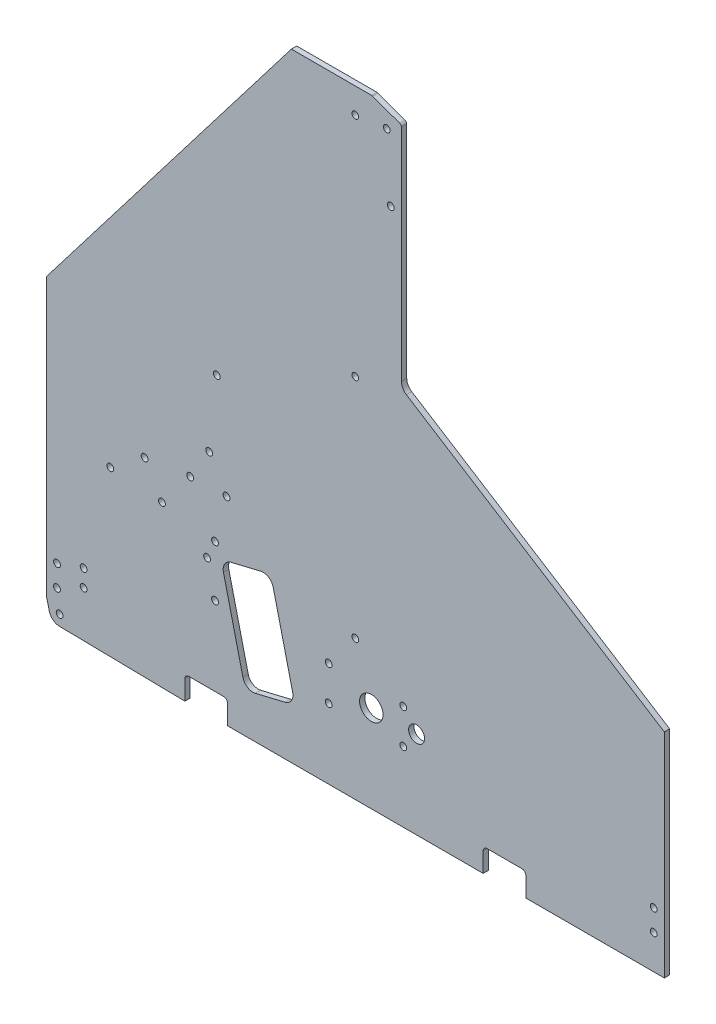
SolidWorks part; units mm, degrees
ref_plane "Front Plane" through (0, 0, 0) normal (0, 0, 1) x (1, 0, 0)
ref_plane "Top Plane" through (0, 0, 0) normal (0, 1, 0) x (1, 0, 0)
ref_plane "Right Plane" through (0, 0, 0) normal (1, 0, 0) x (0, 0, -1)
sketch "Sketch1" plane through (0, 0, 0) normal (0, 0, 1) x (1, 0, 0)
  line L0 (82.55, -20.32) -> (82.55, -6.35)
  line L2 (0, 0) -> (0, 157.48)
  line L4 (368.3, -20.32) -> (368.3, 106.68)
  line L5 (82.55, -6.35) -> (107.95, -6.35)
  line L6 (107.95, -6.35) -> (107.95, -20.32)
  line L7 (107.95, -20.32) -> (260.35, -20.32)
  line L8 (260.35, -20.32) -> (260.35, -6.35)
  line L9 (260.35, -6.35) -> (285.75, -6.35)
  line L10 (285.75, -6.35) -> (285.75, -20.32)
  line L11 (285.75, -20.32) -> (368.3, -20.32)
  line L12 (361.95, 12.7) -> (368.3, 12.7) construction
  line L13 (0, 0) -> (6.35, 0) construction
  line L14 (0.1896, -7.8901) -> (1.7771, -14.2401)
  line L15 (7.8295, -19.0491) -> (82.55, -20.32)
  line L16 (0, 0) -> (0, -6.35)
  line L17 (85.725, 97.155) -> (82.9754, 95.5675) construction
  line L18 (97.0634, 115.6163) -> (58.5686, 93.3913) construction
  line L19 (97.0634, 115.6163) -> (107.3822, 97.7437) construction
  line L20 (58.5686, 93.3913) -> (68.8873, 75.5187) construction
  line L21 (107.3822, 97.7437) -> (68.8873, 75.5187) construction
  line L22 (97.0634, 115.6163) -> (68.8873, 75.5187) construction
  line L23 (58.5686, 93.3913) -> (107.3822, 97.7437) construction
  line L24 (7.9375, -12.7) -> (95.7973, 60.4105) construction
  line L25 (184.15, 62.98) -> (184.15, 197.98) construction
  line L26 (184.15, 197.98) -> (184.15, 332.98) construction
  line L27 (355.6, 335.28) -> (330.2, 335.28) construction
  line L28 (330.2, 335.28) -> (330.2, 220.98) construction
  line L29 (330.2, 220.98) -> (355.6, 220.98) construction
  line L30 (355.6, 220.98) -> (355.6, 335.28) construction
  line L31 (184.15, 347.98) -> (184.15, 269.4703) construction
  line L32 (12.7, 335.28) -> (38.1, 335.28) construction
  line L33 (38.1, 335.28) -> (38.1, 220.98) construction
  line L34 (12.7, 220.98) -> (12.7, 335.28) construction
  line L35 (38.1, 220.98) -> (12.7, 220.98) construction
  line L36 (194.15, 347.98) -> (211.6138, 341.63)
  line L37 (184.15, 347.98) -> (146.05, 347.98)
  line L38 (184.15, 347.98) -> (194.15, 347.98)
  line L39 (348.5362, 347.98) -> (413.4623, 347.98)
  line L40 (348.5362, 347.98) -> (211.6138, 347.98) construction
  line L42 (146.05, 347.98) -> (0, 157.48)
  line L44 (211.6138, 341.63) -> (211.6138, 205.74)
  line L45 (211.6138, 205.74) -> (368.3, 106.68)
  line L46 (194.15, 347.98) -> (-141.0713, 347.98) construction
  circle A0 centre (6.35, 0) radius 2.032
  circle A1 centre (6.35, 12.7) radius 2.032
  circle A2 centre (361.95, 0) radius 2.032
  circle A3 centre (361.95, 12.7) radius 2.032
  arc A5 (1.7771, -14.2401) -> (7.8295, -19.0491) centre (7.9375, -12.7) ccw
  circle A6 centre (7.9375, -12.7) radius 2.032
  arc A7 (0, -6.35) -> (0.1896, -7.8901) centre (6.35, -6.35) ccw
  circle A8 centre (38.1, 78.105) radius 2.032
  circle A9 centre (85.725, 97.155) radius 2.032
  circle A10 centre (58.5686, 93.3913) radius 2.032
  circle A11 centre (68.8873, 75.5187) radius 2.032
  circle A12 centre (107.3822, 97.7437) radius 2.032
  circle A13 centre (97.0634, 115.6163) radius 2.032
  circle A14 centre (95.7973, 60.4105) radius 2.032
  circle A15 centre (184.15, 62.98) radius 2
  circle A16 centre (184.15, 197.98) radius 2
  circle A17 centre (184.15, 332.98) radius 2
  circle A18 centre (63.5, 316.23) radius 2.032
  circle A19 centre (101.6, 157.48) radius 2.032
  circle A20 centre (355.6, 335.28) radius 2.032
  circle A21 centre (330.2, 335.28) radius 2.032
  circle A22 centre (355.6, 220.98) radius 2.032
  circle A23 centre (330.2, 220.98) radius 2.032
  circle A24 centre (12.7, 335.28) radius 2.032
  circle A25 centre (38.1, 335.28) radius 2.032
  circle A26 centre (12.7, 220.98) radius 2.032
  circle A27 centre (38.1, 220.98) radius 2.032
  circle A28 centre (202.8819, 335.28) radius 2
  circle A29 centre (205.2638, 296.418) radius 2.032
  point P82 (184.15, 347.98)
  point P83 (202.8819, 344.805)
  dimension "D6" = 4.064
  dimension "D10" = 6.35
  dimension "D11" = 4.064
  dimension "D17" = 38.1
  dimension "D27" = 4
  dimension "D31" = 4.064
  dimension "D32" = 38.1
  dimension "D36" = 4.064
  dimension "D47" = 45.212
  dimension "D48" = 4.064
  dimension "D2" = 127
  dimension "D3" = 13.97
  dimension "D4" = 25.4
  dimension "D5" = 152.4
  dimension "D7" = 12.7
  dimension "D8" = 6.35
  dimension "D9" = 20.32
  dimension "D12" = 12.7
  dimension "D13" = 1.5875
  dimension "D14" = 82.55
  dimension "D15" = 368.3
  dimension "D16" = 6.35
  dimension "D18" = 98.425
  dimension "D19" = 47.625
  dimension "D20" = 19.05
  dimension "D21" = 3.175
  dimension "D22" = 60
  dimension "D23" = 20.6375
  dimension "D24" = 44.45
  dimension "D25" = 38.1
  dimension "D26" = 114.3
  dimension "D28" = 135
  dimension "D29" = 12.7
  dimension "D30" = 15
  dimension "D33" = 63.5
  dimension "D34" = 27.4638
  dimension "D35" = 101.6
  dimension "D37" = 114.3
  dimension "D38" = 25.4
  dimension "D39" = 12.7
  dimension "D40" = 157.48
  dimension "D41" = 142.24
  dimension "D42" = 368.3
  dimension "D43" = 10
  dimension "D44" = 6.35
  dimension "D45" = 31.75
  dimension "D46" = 6.35
  dimension "D49" = 6.35
extrude "Boss-Extrude1" add sketch "Sketch1" along normal blind 3.175 contours L16 A7 L14 A5 L15 L2 A0 A1 A6 region at (167.8922, 118.3155, 0)
fillet "Fillet1" radius 2.286 4 edges at (285.75, -6.35, 1.5875) (107.95, -6.35, 1.5875) (260.35, -6.35, 1.5875) (82.55, -6.35, 1.5875)
fillet "Fillet2" radius 6.35 1 edges at (211.6138, 205.74, 1.5875)
sketch "Sketch2" plane through (0, 0, 0) normal (0, 0, -1) x (-1, 0, 0)
  circle A0 centre (-100.5528, 71.086) radius 2.032 construction
  circle A1 centre (-100.5528, 40.606) radius 2.032 construction
  circle A2 centre (-22.225, 18.2025) radius 2.032 construction
  circle A3 centre (-22.225, 8.0425) radius 2.032 construction
  circle A4 centre (-100.5528, 71.086) radius 2.032
  circle A5 centre (-100.5528, 40.606) radius 2.032
  circle A6 centre (-22.225, 18.2025) radius 2.032
  circle A7 centre (-22.225, 8.0425) radius 2.032
extrude "Cut-Extrude1" cut sketch "Sketch2" against normal through all
fillet "Fillet3" radius 1.5875 2 edges at (211.6138, 341.63, 1.5875) (194.15, 347.98, 1.5875)
sketch "Sketch3" plane through (0, 0, 3.175) normal (0, 0, 1) x (1, 0, 0)
  line L0 (132.9524, 63.2646) -> (132.7215, 64.2281) construction
  line L1 (128.3814, 66.8897) -> (110.6828, 62.6472) construction
  line L2 (114.5132, 58.4237) -> (126.8822, 61.3887) construction
  line L3 (108.0212, 58.3071) -> (108.2522, 57.3436) construction
  line L4 (131.2006, 57.703) -> (140.0164, 20.9265) construction
  line L5 (144.0993, 16.7636) -> (132.9524, 63.2646) construction
  line L6 (108.2522, 57.3436) -> (119.3991, 10.8426) construction
  line L7 (121.1509, 16.4042) -> (112.3351, 53.1807) construction
  line L8 (119.3991, 10.8426) -> (119.6301, 9.8791) construction
  line L9 (144.3303, 15.8001) -> (144.0993, 16.7636) construction
  line L10 (137.8383, 15.6835) -> (125.4694, 12.7185) construction
  line L11 (123.9701, 7.2175) -> (141.6687, 11.4601) construction
  line L12 (132.9524, 63.2646) -> (132.7215, 64.2281)
  line L13 (128.3814, 66.8897) -> (110.6828, 62.6472)
  line L14 (114.5132, 58.4237) -> (126.8822, 61.3887)
  line L15 (108.0212, 58.3071) -> (108.2522, 57.3436)
  line L16 (131.2006, 57.703) -> (140.0164, 20.9265)
  line L17 (144.0993, 16.7636) -> (132.9524, 63.2646)
  line L18 (108.2522, 57.3436) -> (119.3991, 10.8426)
  line L19 (121.1509, 16.4042) -> (112.3351, 53.1807)
  line L20 (119.3991, 10.8426) -> (119.6301, 9.8791)
  line L21 (144.3303, 15.8001) -> (144.0993, 16.7636)
  line L22 (137.8383, 15.6835) -> (125.4694, 12.7185)
  line L23 (123.9701, 7.2175) -> (141.6687, 11.4601)
  line L24 (127.7894, 69.3598) -> (110.0908, 65.1172)
  line L25 (105.5512, 57.715) -> (105.7822, 56.7515)
  line L26 (105.7822, 56.7515) -> (116.9291, 10.2505)
  line L27 (116.9291, 10.2505) -> (117.16, 9.287)
  line L28 (124.5622, 4.7475) -> (142.2608, 8.99)
  line L29 (146.8003, 16.3922) -> (146.5694, 17.3557)
  line L30 (146.5694, 17.3557) -> (135.4225, 63.8567)
  line L31 (135.4225, 63.8567) -> (135.1915, 64.8202)
  arc A0 (132.7215, 64.2281) -> (128.6308, 66.9403) centre (129.2206, 63.3889) ccw construction
  arc A1 (110.6828, 62.6472) -> (110.4377, 62.5791) centre (111.522, 59.1463) ccw construction
  arc A2 (128.6308, 66.9403) -> (128.3814, 66.8897) centre (129.2206, 63.3889) ccw construction
  arc A3 (110.4377, 62.5791) -> (108.0212, 58.3071) centre (111.522, 59.1463) ccw construction
  arc A4 (119.6301, 9.8791) -> (123.7207, 7.1669) centre (123.1309, 10.7183) ccw construction
  arc A5 (141.9139, 11.5281) -> (144.3303, 15.8001) centre (140.8295, 14.9609) ccw construction
  arc A6 (141.6687, 11.4601) -> (141.9139, 11.5281) centre (140.8295, 14.9609) ccw construction
  arc A7 (123.7207, 7.1669) -> (123.9701, 7.2175) centre (123.1309, 10.7183) ccw construction
  arc A8 (132.7215, 64.2281) -> (128.6308, 66.9403) centre (129.2206, 63.3889) ccw
  arc A9 (110.6828, 62.6472) -> (110.4377, 62.5791) centre (111.522, 59.1463) ccw
  arc A10 (128.6308, 66.9403) -> (128.3814, 66.8897) centre (129.2206, 63.3889) ccw
  arc A11 (110.4377, 62.5791) -> (108.0212, 58.3071) centre (111.522, 59.1463) ccw
  arc A12 (119.6301, 9.8791) -> (123.7207, 7.1669) centre (123.1309, 10.7183) ccw
  arc A13 (141.9139, 11.5281) -> (144.3303, 15.8001) centre (140.8295, 14.9609) ccw
  arc A14 (141.6687, 11.4601) -> (141.9139, 11.5281) centre (140.8295, 14.9609) ccw
  arc A15 (123.7207, 7.1669) -> (123.9701, 7.2175) centre (123.1309, 10.7183) ccw
  arc A16 (110.0908, 65.1172) -> (109.6726, 65.0012) centre (111.522, 59.1463) ccw
  arc A17 (109.6726, 65.0012) -> (105.5512, 57.715) centre (111.522, 59.1463) ccw
  arc A18 (117.16, 9.287) -> (124.1369, 4.6613) centre (123.1309, 10.7183) ccw
  arc A19 (124.1369, 4.6613) -> (124.5622, 4.7475) centre (123.1309, 10.7183) ccw
  arc A20 (142.2608, 8.99) -> (142.6789, 9.1061) centre (140.8295, 14.9609) ccw
  arc A21 (142.6789, 9.1061) -> (146.8003, 16.3922) centre (140.8295, 14.9609) ccw
  arc A22 (135.1915, 64.8202) -> (128.2147, 69.446) centre (129.2206, 63.3889) ccw
  arc A23 (128.2147, 69.446) -> (127.7894, 69.3598) centre (129.2206, 63.3889) ccw
  ellipse E0 centre (124.5974, 48.8487) end of major axis (128.5376, 61.3578) minor radius 6 (131.2006, 57.703) -> (126.8822, 61.3887) ccw construction
  ellipse E1 centre (122.2349, 48.2824) end of major axis (113.0518, 57.6456) minor radius 6 (114.5132, 58.4237) -> (112.3351, 53.1807) ccw construction
  ellipse E2 centre (127.7541, 25.2585) end of major axis (131.6942, 37.7675) minor radius 6 (121.1509, 16.4042) -> (125.4694, 12.7185) ccw construction
  ellipse E3 centre (130.1166, 25.8248) end of major axis (139.2998, 16.4616) minor radius 6 (137.8383, 15.6835) -> (140.0164, 20.9265) ccw construction
  ellipse E4 centre (124.5974, 48.8487) end of major axis (128.5376, 61.3578) minor radius 6 (131.2006, 57.703) -> (126.8822, 61.3887) ccw
  ellipse E5 centre (122.2349, 48.2824) end of major axis (131.4181, 38.9192) minor radius 6 (114.5132, 58.4237) -> (112.3351, 53.1807) ccw
  ellipse E6 centre (127.7541, 25.2585) end of major axis (123.8139, 12.7495) minor radius 6 (121.1509, 16.4042) -> (125.4694, 12.7185) ccw
  ellipse E7 centre (130.1166, 25.8248) end of major axis (139.2998, 16.4616) minor radius 6 (137.8383, 15.6835) -> (140.0164, 20.9265) ccw
  dimension "D1" = 2.54
extrude "Cut-Extrude2" cut sketch "Sketch3" against normal through all contours A22 A23 L24 A16 A17 L25 L26 L27 A18 A19 L28 A20 A21 L29 L30 L31 A15 A12 L20 L18 L15 A11 A9 L13 A10 A8 L12 L17 L21 A13 A14 L23 | A12 A15 L23 A14 A13 L21 L17 L12 A8 A10 L13 A9 A11 L15 L18 L20 E7 L22 E6 L19 E5 L14 E4 L16 | L22 E7 L16 E4 L14 E5 L19 E6 region at (137.844, 39.8506, 3.175) region at (126.1758, 37.0536, 3.175) region at (128.1544, 68.6507, 3.175)
sketch "Sketch4" plane through (0, 0, 3.175) normal (0, 0, 1) x (1, 0, 0)
  line L0 (107.3822, 97.7437) -> (68.8873, 75.5187) construction
  line L1 (168.275, 21.4312) -> (212.725, 21.4312) construction
  line L2 (168.275, 21.4312) -> (168.275, 42.0687) construction
  line L3 (168.275, 42.0687) -> (212.725, 42.0687) construction
  line L4 (212.725, 21.4312) -> (212.725, 42.0687) construction
  line L5 (168.275, 21.4312) -> (212.725, 42.0687) construction
  line L6 (168.275, 42.0687) -> (212.725, 21.4312) construction
  line L7 (97.0634, 115.6163) -> (107.3822, 97.7437) construction
  line L8 (107.95, -20.32) -> (260.35, -20.32) construction
  line L10 (190.5, 31.75) -> (193.675, 31.75) construction
  line L11 (6.35, 12.7) -> (361.95, 12.7) construction
  line L12 (107.95, -6.35) -> (107.95, -20.32) construction
  line L13 (193.675, 31.75) -> (220.6625, 31.75) construction
  line L15 (194.15, 47.98) -> (174.15, 47.98) construction
  line L16 (194.15, 47.98) -> (194.15, 347.98) construction
  line L17 (194.15, 347.98) -> (174.15, 347.98) construction
  line L18 (174.15, 47.98) -> (174.15, 347.98) construction
  line L19 (194.15, 47.98) -> (174.15, 347.98) construction
  line L20 (194.15, 347.98) -> (174.15, 47.98) construction
  circle A0 centre (168.275, 42.0687) radius 2.032
  circle A1 centre (212.725, 42.0687) radius 2.032
  circle A2 centre (212.725, 21.4312) radius 2.032
  circle A3 centre (168.275, 21.4312) radius 2.032
  circle A4 centre (193.675, 31.75) radius 6.985
  circle A5 centre (220.6625, 31.75) radius 4.7625
  circle A7 centre (220.6625, 31.75) radius 14.2875 construction
  circle A8 centre (193.675, 31.75) radius 12.7 construction
  point P0 (190.5, 31.75)
  point P26 (184.15, 197.98)
  dimension "D1" = 4.064
  dimension "D4" = 13.97
  dimension "D7" = 9.525
  dimension "D10" = 25.4
  dimension "D11" = 28.575
  dimension "D2" = 52.07
  dimension "D3" = 3.175
  dimension "D5" = 82.55
  dimension "D6" = 26.9875
  dimension "D8" = 20
  dimension "D9" = 300
extrude "Cut-Extrude3" cut sketch "Sketch4" against normal through all
